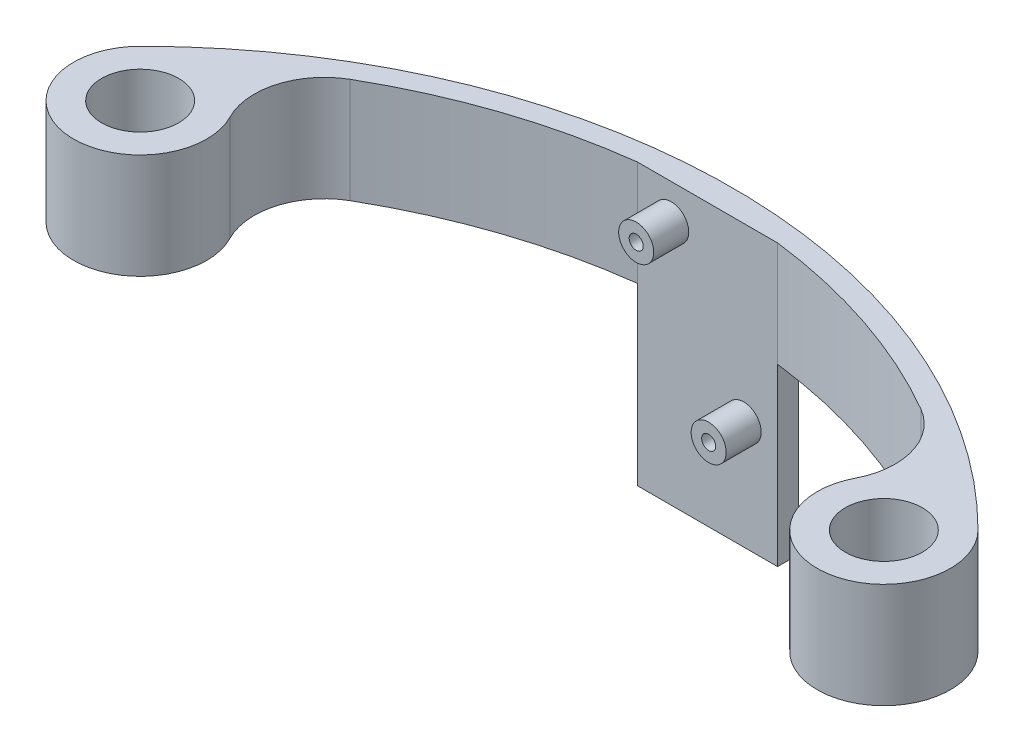
SolidWorks part; units mm, degrees
ref_plane "Front Plane" through (0, 0, 0) normal (0, 0, 1) x (1, 0, 0)
ref_plane "Top Plane" through (0, 0, 0) normal (0, 1, 0) x (1, 0, 0)
ref_plane "Right Plane" through (0, 0, 0) normal (1, 0, 0) x (0, 0, -1)
sketch "Sketch1" plane through (0, 0, 0) normal (0, 0, 1) x (1, 0, 0)
  line L1 (0, 0) -> (20, 0)
  line L2 (0, 0) -> (0, -40)
  line L3 (0, -40) -> (20, -40)
  line L4 (20, 0) -> (20, -40)
  circle A0 centre (4.83, -5) radius 2.5
  circle A5 centre (4.83, -5) radius 1
  circle A10 centre (15.1678, -24.558) radius 1
  circle A11 centre (15.1678, -24.558) radius 2.5
  circle A14 centre (15.1678, -5) radius 2.5 [skipped]
  circle A15 centre (15.1678, -5) radius 1 [skipped]
  circle A16 centre (4.83, -24.558) radius 2.5 [skipped]
  circle A17 centre (4.83, -24.558) radius 1 [skipped]
  dimension "D7" = 2
  dimension "D5" = 2
  dimension "D6" = 5
  dimension "D1" = 20
  dimension "D2" = 40
  dimension "D4" = 5
  dimension "D10" = 4.83
  dimension "D8" = 2
extrude "Boss-Extrude1" add sketch "Sketch1" along normal blind 3 contours A10 | A11 A10 | A5 | A0 A5 | L4 L1 L2 L3 A11 A0
sketch "Sketch2" plane through (0, 0, 3) normal (0, 0, 1) x (1, 0, 0)
  line L4 (20, -40) -> (20, 0)
  line L5 (20, 0) -> (0, 0)
  line L6 (0, 0) -> (0, -40)
  line L7 (0, -40) -> (20, -40)
  line L8 (20, -40) -> (20, 0)
  line L9 (20, 0) -> (0, 0)
  line L10 (0, 0) -> (0, -40)
  line L11 (0, -40) -> (20, -40)
  line L12 (20, 0) -> (0, 0)
  line L13 (20, -40) -> (20, 0)
  line L14 (0, -40) -> (20, -40)
  line L15 (0, 0) -> (0, -40)
  line L16 (20, 0) -> (0, 0)
  line L17 (20, -40) -> (20, 0)
  line L18 (0, -40) -> (20, -40)
  line L19 (0, 0) -> (0, -40)
  circle A1 centre (15.1678, -24.558) radius 2.5
  circle A2 centre (15.1678, -24.558) radius 2.5
  circle A3 centre (15.1678, -24.558) radius 1
  circle A4 centre (15.1678, -24.558) radius 1
  circle A5 centre (4.83, -5) radius 1
  circle A6 centre (4.83, -5) radius 1
  circle A7 centre (4.83, -5) radius 2.5
  circle A8 centre (4.83, -5) radius 2.5
  dimension "D1" = 0
  dimension "D2" = 0
  dimension "D3" = 0
  dimension "D4" = 0
  dimension "D5" = 0
  dimension "D6" = 0
extrude "Boss-Extrude2" add sketch "Sketch2" along normal blind 5 contours A8 A6 | A2 A4 region at (12.7385, -24.558, 3) region at (2.4007, -5, 3)
sketch "Sketch3" plane through (0, 0, 0) normal (0, 1, 0) x (1, 0, 0)
  line L0 (10, 0) -> (10, -220.1513) construction
  line L1 (0, 0) -> (20, 0) construction
  line L2 (20, 0) -> (10, -83.9062)
  line L3 (0, -3) -> (0, 0) construction
  line L4 (-43.05, -30.8902) -> (63.05, -30.8902) construction
  arc A0 (69.7697, -24.1748) -> (-49.7697, -24.1748) centre (10, -83.9062) ccw
  circle A1 centre (10, -83.9062) radius 75 construction
  circle A2 centre (-43.05, -30.8902) radius 5.5
  circle A3 centre (63.05, -30.8902) radius 5.5
  arc A4 (54.6086, -26.5321) -> (69.7697, -24.1748) centre (63.05, -30.8902) ccw
  arc A5 (-49.7697, -24.1748) -> (-34.6086, -26.5321) centre (-43.05, -30.8902) ccw
  arc A7 (50.7177, -13.2812) -> (-30.7177, -13.2812) centre (10, -83.9062) ccw
  arc A8 (-30.7177, -13.2812) -> (-34.6086, -26.5321) centre (-25.723, -21.9446) ccw
  arc A9 (50.7177, -13.2812) -> (54.6086, -26.5321) centre (45.723, -21.9446) cw
  line M5 (20, 0) -> (0, 0)
  line M6 (0, 0) -> (0, -3)
  line M8 (20, -3) -> (20, 0)
  dimension "D2" = 169
  dimension "D3" = 150
  dimension "D5" = 10
  dimension "D1" = 10
  dimension "D4" = 106.1
extrude "Boss-Extrude3" add sketch "Sketch3" against normal blind 15 contours A8 A7 A0 A5 A2 M6 | A7 A9 A4 A0 A3 M8 | A0 M5 region at (10, 0, -0.2376) region at (46.63, 0, 8.4945) region at (-0.6628, 0, 1.5)
